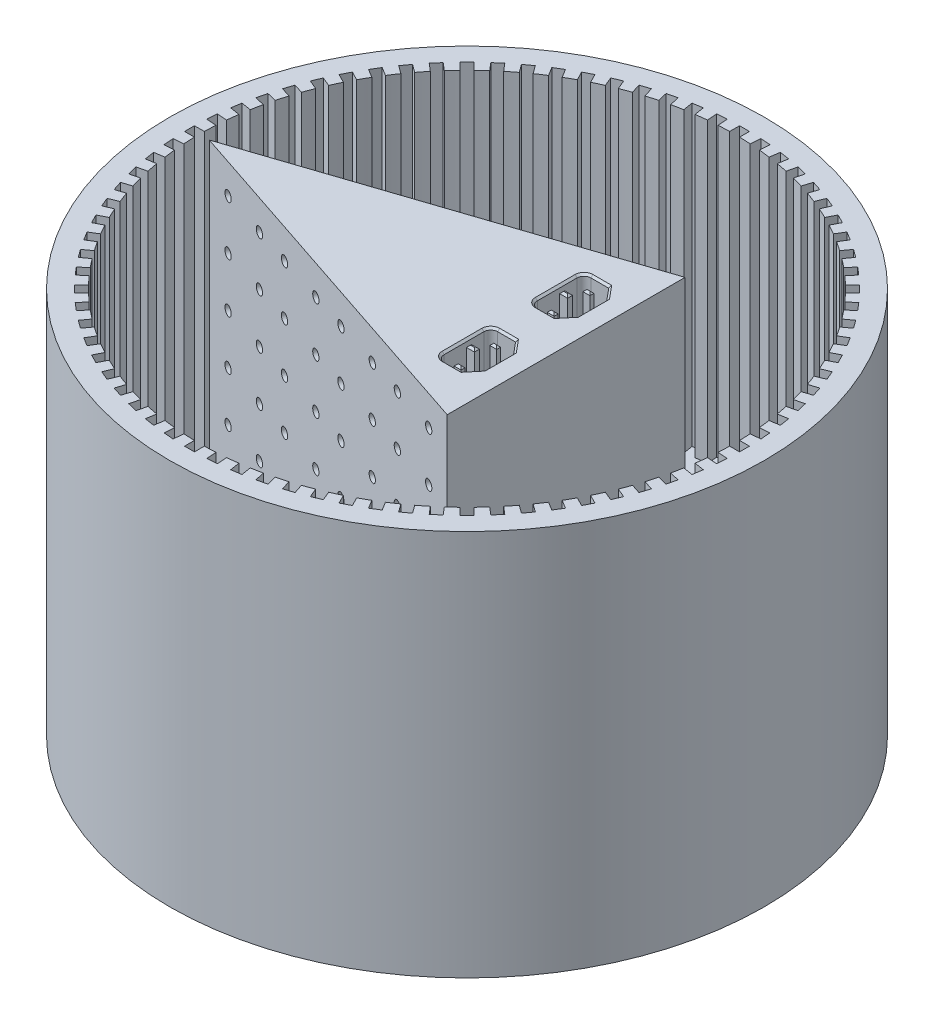
SolidWorks part; units mm, degrees
material "A286 Iron Base Superalloy"
ref_plane "Front Plane" through (0, 0, 0) normal (0, 0, 1) x (1, 0, 0)
ref_plane "Top Plane" through (0, 0, 0) normal (0, 1, 0) x (1, 0, 0)
ref_plane "Right Plane" through (0, 0, 0) normal (1, 0, 0) x (0, 0, -1)
sketch "Sketch1" plane through (0, 0, 0) normal (0, 0, 1) x (1, 0, 0)
  line L0 (0, 0) -> (0, 20) construction
  line L13 (0, 0) -> (15, 0)
  line L14 (15, 0) -> (15, 4.5)
  line L15 (0, 0.5) -> (14, 0.5)
  line L16 (14.5, 1) -> (14.5, 3.5)
  line L17 (14, 4) -> (0, 4)
  line L18 (0, 0.5) -> (0, 0)
  line L19 (0, 4) -> (0, 4.5)
  line L20 (0, 4.5) -> (15, 4.5)
  arc A0 (14, 0.5) -> (14.5, 1) centre (14, 1) ccw
  arc A1 (14.5, 3.5) -> (14, 4) centre (14, 3.5) ccw
  dimension "D7" = 0.5
  dimension "D1" = 20
  dimension "D2" = 15
  dimension "D3" = 0.5
  dimension "D4" = 3.5
  dimension "D5" = 0.5
  dimension "D6" = 0.5
revolve "Revolve1" add sketch "Sketch1" angle 360 about L0
sketch "Sketch2" plane through (0, 0, 0) normal (0, -1, 0) x (1, 0, 0)
  line L0 (0, 0) -> (15, 0) construction
  line L1 (0, 0) -> (0, 15) construction
  circle A0 centre (10, 3.5) radius 1.5
  circle A1 centre (10, -3.5) radius 1.5
  circle A2 centre (0, 0) radius 15 construction
  dimension "D2" = 3
  dimension "D3" = 3.5
  dimension "D1" = 10
extrude "Cut-Extrude1" cut sketch "Sketch2" against normal up to surface (4.5 mm away) and the other way through all up to face at (0, 4.5, -15)
sketch "Sketch4" plane through (0, 4.5, 0) normal (0, 1, 0) x (1, 0, 0)
  line L4 (5, -6) -> (-13, 0)
  line L5 (-13, 0) -> (5, 6)
  line L6 (5, 6) -> (5, -6)
  line L7 (0, 0) -> (15, 0) construction
  line L8 (10, 5) -> (10, -5) construction
  circle A0 centre (10, 3.5) radius 1.5 construction
  circle A1 centre (10, -3.5) radius 1.5 construction
  circle A2 centre (0, 0) radius 15 construction
  point P6 (5, 0)
  dimension "D1" = 5
  dimension "D2" = 12
  dimension "D3" = 18
extrude "Boss-Extrude1" add sketch "Sketch4" along normal blind 15
sketch "Sketch5" plane through (-1.3, 0, 3.9) normal (-0.3162, 0, 0.9487) x (0.9487, 0, 0.3162)
  line L0 (6.6408, 18) -> (-12.3329, 18) construction
  line L1 (6.6408, 19.5) -> (6.6408, 4.5) construction
  line L2 (-12.3329, 19.5) -> (-12.3329, 4.5) construction
  line L3 (-12.3329, 19.5) -> (6.6408, 19.5) construction
  line L7 (-6.8592, 18) -> (-25.8329, 18) construction
  line L8 (-2.3592, 18) -> (-21.3329, 18) construction
  line L9 (2.1408, 18) -> (-16.8329, 18) construction
  circle A0 centre (2.6671, 18) radius 0.25
  circle A1 centre (5.1671, 18) radius 0.25
  circle A2 centre (-1.8329, 18) radius 0.25
  circle A3 centre (0.6671, 18) radius 0.25
  circle A4 centre (-6.3329, 18) radius 0.25
  circle A5 centre (-3.8329, 18) radius 0.25
  circle A6 centre (-10.8329, 18) radius 0.25
  circle A7 centre (-8.3329, 18) radius 0.25
  dimension "D1" = 0.5
  dimension "D3" = 2.5
  dimension "D6" = 1.5
  dimension "D2" = 1.5
  dimension "D4" = 2
  dimension "D5" = 4
extrude "Cut-Extrude2" cut sketch "Sketch5" against normal blind 0.5
pattern_linear "LPattern1" count 6 spacing 2.5 along (0, -1, 0) of "Cut-Extrude2"
mirror "Mirror1" about plane through (0, 0, 0) normal (0, 0, 1) of "LPattern1"
sketch "Sketch6" plane through (0, 19.5, 0) normal (0, 1, 0) x (1, 0, 0)
  line L0 (3, 5.3333) -> (3, -5.3333) construction
  line L1 (5, 6) -> (-13, 0) construction
  line L2 (-13, 0) -> (5, -6) construction
  line L3 (0, 0) -> (5, 0) construction
  line L4 (5, -6) -> (5, 6) construction
  line L5 (2.2, -3.35) -> (2.2, -1.35)
  line L6 (2.55, -1) -> (3.45, -1)
  line L7 (3.45, -1) -> (3.95, -1.6)
  line L8 (3.95, -1.6) -> (3.95, -3.1)
  line L9 (3.95, -3.1) -> (3.45, -3.7)
  line L10 (3.45, -3.7) -> (2.55, -3.7)
  line L11 (3.45, 3.7) -> (2.55, 3.7)
  line L12 (3.95, 3.1) -> (3.45, 3.7)
  line L13 (3.95, 1.6) -> (3.95, 3.1)
  line L14 (3.45, 1) -> (3.95, 1.6)
  line L15 (2.55, 1) -> (3.45, 1)
  line L16 (2.2, 3.35) -> (2.2, 1.35)
  arc A2 (2.2, -1.35) -> (2.55, -1) centre (2.55, -1.35) cw
  arc A3 (2.55, -3.7) -> (2.2, -3.35) centre (2.55, -3.35) cw
  arc A4 (2.2, 1.35) -> (2.55, 1) centre (2.55, 1.35) ccw
  arc A5 (2.55, 3.7) -> (2.2, 3.35) centre (2.55, 3.35) ccw
  point P21 (3, -1)
  dimension "D1" = 2
  dimension "D2" = 0.35
  dimension "D3" = 0.5
  dimension "D4" = 1.5
  dimension "D5" = 2
  dimension "D6" = 1
  dimension "D7" = 1.75
  dimension "D8" = 0.9
extrude "Cut-Extrude3" cut sketch "Sketch6" against normal blind 2.5
sketch "Sketch7" plane through (0, 17, 0) normal (0, 1, 0) x (1, 0, 0)
  line L0 (2.55, -3.7) -> (3.45, -3.7) construction
  line L1 (2.7, -3.35) -> (3.05, -3.35)
  line L2 (2.7, -3.35) -> (2.7, -3.15)
  line L3 (2.7, -3.15) -> (3.05, -3.15)
  line L4 (3.05, -3.35) -> (3.05, -3.15)
  line L5 (2.7, -3.35) -> (3.05, -3.15) construction
  line L6 (2.7, -3.15) -> (3.05, -3.35) construction
  line L7 (3.95, -3.1) -> (3.95, -1.6) construction
  line L8 (3.95, -2.35) -> (2.2, -2.35) construction
  line L9 (2.2, -1.35) -> (2.2, -3.35) construction
  line L10 (2.7, -1.55) -> (3.05, -1.55)
  line L11 (3.05, -1.35) -> (3.05, -1.55)
  line L12 (2.7, -1.35) -> (3.05, -1.35)
  line L13 (2.7, -1.35) -> (2.7, -1.55)
  point P0 (2.875, -3.25)
  dimension "D1" = 0.35
  dimension "D2" = 0.9
  dimension "D3" = 0.35
  dimension "D4" = 0.2
extrude "Boss-Extrude2" add sketch "Sketch7" along normal blind 2.25
sketch "Sketch8" plane through (0, 17, 0) normal (0, 1, 0) x (1, 0, 0)
  line L0 (2.2, -1.35) -> (2.2, -3.35) construction
  line L1 (2.85, -2.475) -> (2.45, -2.475)
  line L2 (2.85, -2.475) -> (2.85, -2.225)
  line L3 (2.85, -2.225) -> (2.45, -2.225)
  line L4 (2.45, -2.475) -> (2.45, -2.225)
  line L5 (2.85, -2.475) -> (2.45, -2.225) construction
  line L6 (2.85, -2.225) -> (2.45, -2.475) construction
  line L7 (2.2, -2.35) -> (3.95, -2.35) construction
  line L8 (3.95, -3.1) -> (3.95, -1.6) construction
  point P0 (2.65, -2.35)
  dimension "D1" = 0.25
  dimension "D2" = 0.25
  dimension "D3" = 0.4
extrude "Boss-Extrude3" add sketch "Sketch8" along normal blind 2.5 contours L3 L4 L1 L2
mirror "Mirror2" about plane through (0, 0, 0) normal (0, 0, 1) of "Boss-Extrude3", "Boss-Extrude2"
chamfer "Chamfer1" distance 0.1 angle 45 40 edges at (2.875, 19.25, 3.35) (2.7, 19.25, 3.25) (2.875, 19.25, 3.15) (3.05, 19.25, 3.25) (3, 19.5, 1) (3, 19.5, 3.7) (2.3025, 19.5, 1.1025) (2.3025, 19.5, 3.5975) (2.2, 19.5, 2.35) (2.7, 19.25, 1.45) (2.875, 19.25, 1.55) (2.875, 19.25, 1.35) (3.05, 19.25, 1.45) (2.65, 19.5, 2.475) (2.45, 19.5, 2.35) (2.65, 19.5, 2.225) (2.85, 19.5, 2.35) (3.7, 19.5, 3.4) (3.95, 19.5, 2.35) (3.7, 19.5, 1.3) (2.875, 19.25, -3.15) (2.7, 19.25, -3.25) (2.875, 19.25, -3.35) (3.05, 19.25, -3.25) (2.875, 19.25, -1.55) (3.05, 19.25, -1.45) (2.875, 19.25, -1.35) (2.7, 19.25, -1.45) (2.65, 19.5, -2.225) (2.45, 19.5, -2.35) (2.65, 19.5, -2.475) (2.85, 19.5, -2.35) (3.95, 19.5, -2.35) (3.7, 19.5, -3.4) (3, 19.5, -3.7) (2.3025, 19.5, -3.5975) (3.7, 19.5, -1.3) (3, 19.5, -1) (2.3025, 19.5, -1.1025) (2.2, 19.5, -2.35)
sketch "Sketch10" plane through (5, 0, 0) normal (1, 0, 0) x (0, 0, -1)
  line L0 (-6, 7) -> (6, 7) construction
  line L1 (-6, 19.5) -> (-6, 4.5) construction
  line L2 (6, 19.5) -> (6, 4.5) construction
  line L3 (-6, 4.5) -> (6, 4.5) construction
  line L4 (0, 0) -> (0, 19.5) construction
  line L5 (-6, 19.5) -> (6, 19.5) construction
  circle A0 centre (-3.5, 7.5103) radius 1.5
  circle A1 centre (3.5, 7.5103) radius 1.5
  circle A2 centre (-3.5, 7.5103) radius 1.625
  circle A3 centre (3.5, 7.5103) radius 1.625
  dimension "D3" = 3
  dimension "D4" = 3.25
  dimension "D1" = 2.5
  dimension "D2" = 3.5
extrude "Boss-Extrude4" add sketch "Sketch10" along normal blind 0.35
fillet "Fillet1" radius 1 2 edges at (5, 7.5103, 5.125) (5, 7.5103, -1.875)
sketch "Sketch12" plane through (0, 4.5, 0) normal (0, 1, 0) x (1, 0, 0)
  line L3 (0, 0) -> (0, 15) construction
  circle A0 centre (0, 0) radius 15
  circle A1 centre (0, 0) radius 13.5
  dimension "D1" = 27
extrude "Boss-Extrude5" add sketch "Sketch12" along normal blind 15
sketch "Sketch13" plane through (0, 19.5, 0) normal (0, 1, 0) x (1, 0, 0)
  line L0 (0, 0) -> (0, 15) construction
  line L1 (-0.25, 13.4977) -> (-0.25, 13.9977)
  line L2 (-0.25, 13.9977) -> (0.25, 13.9977)
  line L3 (0.25, 13.9977) -> (0.25, 13.4977)
  circle A0 centre (0, 0) radius 15 construction
  arc A1 (-0.25, 13.4977) -> (0.25, 13.4977) centre (0, 0) cw
  circle A2 centre (0, 0) radius 13.5 construction
  point P12 (0, 13.9977)
  dimension "D1" = 0.5
  dimension "D2" = 0.5
extrude "Cut-Extrude4" cut sketch "Sketch13" against normal blind 15
pattern_circular "CirPattern1" count 80 over 360 about axis through (0, 19.5, 0) along (0, -1, 0) of "Cut-Extrude4" reverse direction yes
scale "Scale1" scale about centroid uniform scaling yes scale factor 5
